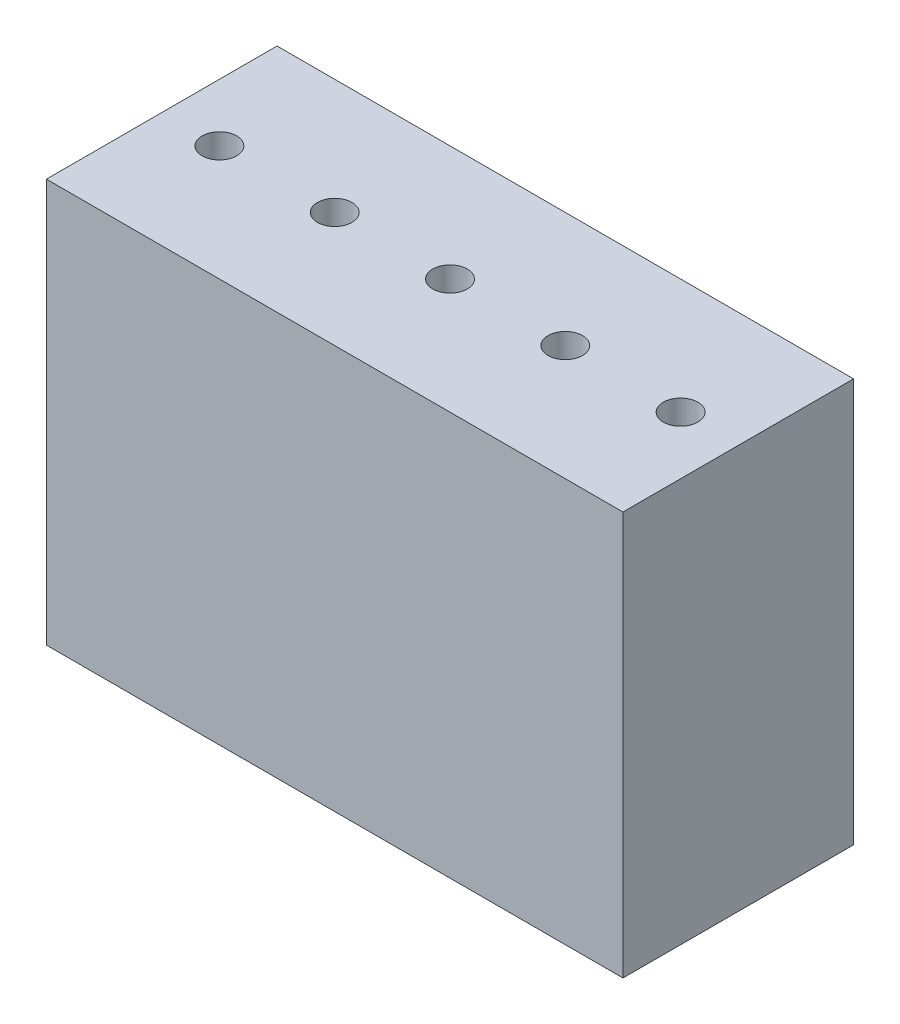
SolidWorks part; units mm, degrees
ref_plane "Front Plane" through (0, 0, 0) normal (0, 0, 1) x (1, 0, 0)
ref_plane "Top Plane" through (0, 0, 0) normal (0, 1, 0) x (1, 0, 0)
ref_plane "Right Plane" through (0, 0, 0) normal (1, 0, 0) x (0, 0, -1)
sketch "Sketch1" plane through (0, 0, 0) normal (0, 1, 0) x (1, 0, 0)
  line L0 (0, 10) -> (50, 10) construction
  line L1 (0, 0) -> (50, 0)
  line L2 (0, 0) -> (0, 20)
  line L3 (0, 20) -> (50, 20)
  line L4 (50, 0) -> (50, 20)
  line L5 (5, 10) -> (15, 10) construction
  line L6 (25, 20) -> (25, 0) construction
  circle A0 centre (5, 10) radius 1.5
  circle A1 centre (15, 10) radius 1.5
  circle A2 centre (25, 10) radius 1.5
  circle A3 centre (35, 10) radius 1.5
  circle A4 centre (45, 10) radius 1.5
  point P21 (0, 0)
  dimension "D3" = 3
  dimension "D1" = 20
  dimension "D2" = 50
  dimension "D5" = 10
  dimension "D4" = 5
extrude "Boss-Extrude1" add sketch "Sketch1" along normal blind 35
